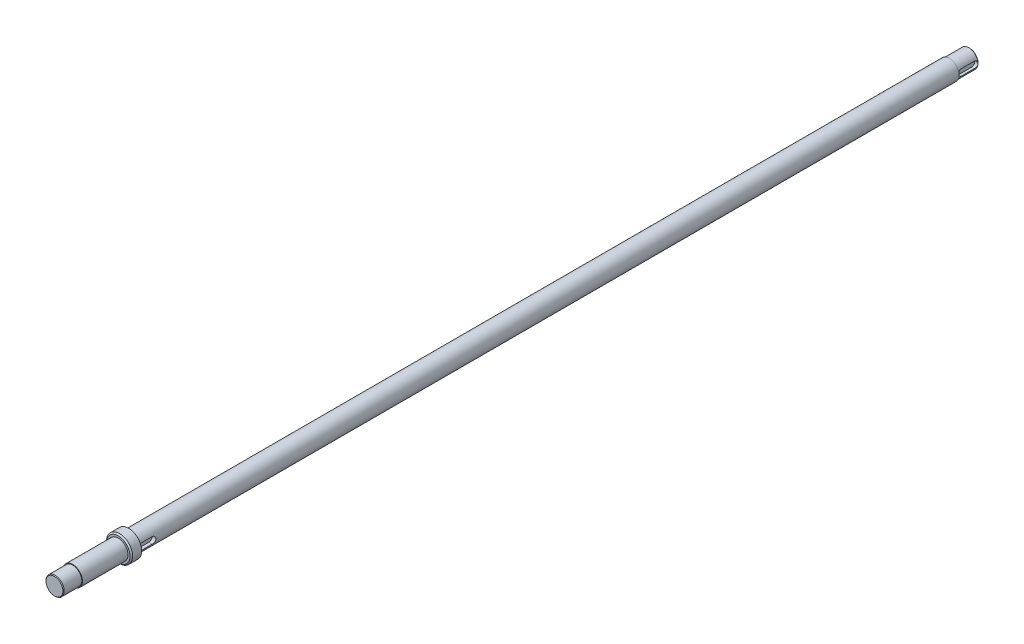
SolidWorks part; units mm, degrees
ref_plane "前视基准面" through (0, 0, 0) normal (0, 0, 1) x (1, 0, 0)
ref_plane "上视基准面" through (0, 0, 0) normal (0, 1, 0) x (1, 0, 0)
ref_plane "右视基准面" through (0, 0, 0) normal (1, 0, 0) x (0, 0, -1)
other "Configuration Table"
sketch "草图1" plane through (0, 0, 0) normal (1, 0, 0) x (0, 0, -1)
  line L0 (0, 0) -> (0, 7)
  line L1 (0, 7) -> (14, 7)
  line L2 (14, 7) -> (14, 7.5)
  line L3 (14, 7.5) -> (49, 7.5)
  line L4 (49, 7.5) -> (49, 10)
  line L5 (49, 10) -> (57, 10)
  line L6 (57, 10) -> (57, 7.5)
  line L7 (57, 7.5) -> (687.5, 7.5)
  line L8 (687.5, 7.5) -> (687.5, 7)
  line L9 (687.5, 7) -> (703, 7)
  line L10 (703, 7) -> (703, 0)
  line L11 (703, 0) -> (0, 0)
  line L12 (0, 0) -> (-37.1247, 0) construction
  dimension "D1" = 14
  dimension "D2" = 15
  dimension "D3" = 20
  dimension "D4" = 14
  dimension "D5" = 35
  dimension "D6" = 8
  dimension "D7" = 673.5
  dimension "D8" = 15.5
revolve "旋转1" add sketch "草图1" angle 360 about L12
ref_plane "基准面1" through (4.5, 0, 0) normal (1, 0, 0) x (0, 0, -1)
sketch "草图2" plane through (4.5, 0, 0) normal (1, 0, 0) x (0, 0, -1)
  line L0 (60, 0) -> (68, 0) construction
  line L1 (60, 2.5) -> (68, 2.5)
  line L2 (60, -2.5) -> (68, -2.5)
  line L3 (690, 0) -> (700, 0) construction
  line L4 (690, 2.5) -> (700, 2.5)
  line L5 (690, -2.5) -> (700, -2.5)
  line L6 (57, -7.5) -> (57, 7.5) construction
  line L7 (687.5, -7.5) -> (687.5, 7.5) construction
  arc A0 (60, 2.5) -> (60, -2.5) centre (60, 0) ccw
  arc A1 (68, -2.5) -> (68, 2.5) centre (68, 0) ccw
  arc A2 (690, 2.5) -> (690, -2.5) centre (690, 0) ccw
  arc A3 (700, -2.5) -> (700, 2.5) centre (700, 0) ccw
  point P2 (64, 0)
  point P10 (695, 0)
  point P15 (72.7049, 0)
  point P18 (695.2084, 0)
  dimension "D1" = 8
  dimension "D2" = 3
  dimension "D3" = 5
  dimension "D4" = 10
  dimension "D5" = 5
extrude "切除-拉伸1" cut sketch "草图2" along normal through all contours L2 A1 L1 A0 | L5 A3 L4 A2
chamfer "倒角1" distance 1 angle 45 1 edges at (-10, 0, -49)
sketch "草图3" plane through (0, 0, -703) normal (0, 0, -1) x (-1, 0, 0)
  circle A0 centre (0, 0) radius 3
  dimension "D1" = 6
extrude "切除-拉伸2" cut sketch "草图3" against normal blind 15
chamfer "倒角2" distance 0.5 angle 45 3 edges at (-7, 0, -703) (-7, 0, 0) (-3, 0, -703)
